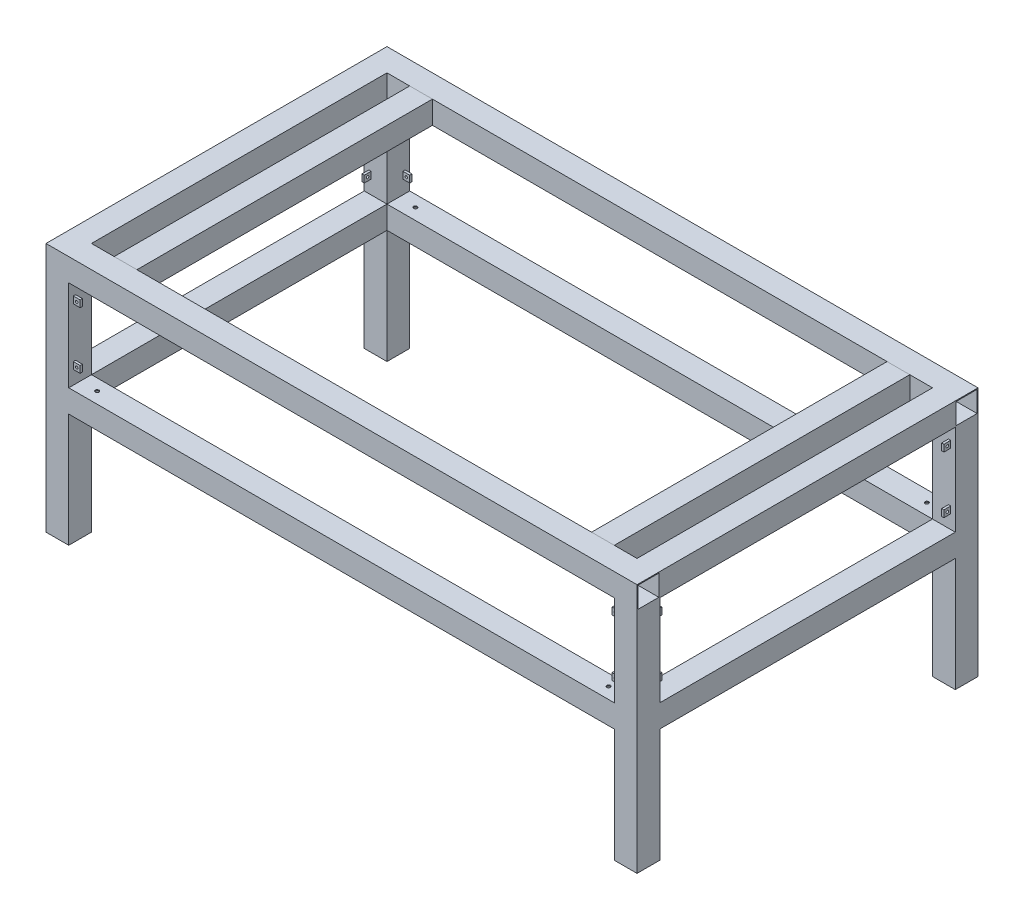
SolidWorks part; units mm, degrees
ref_plane "Plan de face" through (0, 0, 0) normal (0, 0, 1) x (1, 0, 0)
ref_plane "Plan de dessus" through (0, 0, 0) normal (0, 1, 0) x (1, 0, 0)
ref_plane "Plan de droite" through (0, 0, 0) normal (1, 0, 0) x (0, 0, -1)
sketch "Esquisse1" plane through (0, 0, 0) normal (0, 1, 0) x (1, 0, 0)
  line L1 (0, 0) -> (1300, 0)
  line L2 (0, 0) -> (0, 750)
  line L3 (0, 750) -> (1300, 750)
  line L4 (1300, 0) -> (1300, 750)
  line L5 (50, 700) -> (1250, 700)
  line L6 (50, 700) -> (50, 50)
  line L7 (50, 50) -> (1250, 50)
  line L8 (1250, 700) -> (1250, 50)
  dimension "D1" = 1300
  dimension "D2" = 750
  dimension "D3" = 50
  dimension "D4" = 50
  dimension "D5" = 50
  dimension "D6" = 50
extrude "Boss.-Extru.1" add sketch "Esquisse1" against normal blind 550
sketch "Esquisse2" plane through (0, 0, 0) normal (0, 0, 1) x (1, 0, 0)
  line L0 (0, 0) -> (1300, 0) construction
  line L1 (50, -50) -> (1250, -50)
  line L2 (50, -50) -> (50, -250)
  line L3 (50, -250) -> (1250, -250)
  line L4 (1250, -50) -> (1250, -250)
  line L5 (50, -300) -> (1250, -300)
  line L6 (50, -300) -> (50, -550)
  line L7 (50, -550) -> (1250, -550)
  line L8 (1250, -300) -> (1250, -550)
  line L9 (0, -550) -> (1300, -550) construction
  line L10 (1300, -550) -> (1300, 0) construction
  line L11 (0, -550) -> (0, 0) construction
  point P12 (1250, -425)
  dimension "D1" = 50
  dimension "D2" = 50
  dimension "D3" = 200
  dimension "D4" = 0
  dimension "D5" = 50
  dimension "D6" = 50
  dimension "D7" = 50
  dimension "D8" = 50
extrude "Enlèv. mat.-Extru.1" cut sketch "Esquisse2" against normal through all
sketch "Esquisse3" plane through (0, 0, 0) normal (-1, 0, 0) x (0, 0, 1)
  line L0 (-750, -550) -> (0, -550) construction
  line L1 (-700, -50) -> (-50, -50)
  line L2 (-700, -50) -> (-700, -250)
  line L3 (-700, -250) -> (-50, -250)
  line L4 (-50, -50) -> (-50, -250)
  line L5 (-700, -300) -> (-50, -300)
  line L6 (-700, -300) -> (-700, -550)
  line L7 (-700, -550) -> (-50, -550)
  line L8 (-50, -300) -> (-50, -550)
  line L9 (-750, 0) -> (0, 0) construction
  line L10 (0, -550) -> (0, 0) construction
  line L11 (-750, -550) -> (-750, 0) construction
  dimension "D1" = 50
  dimension "D2" = 50
  dimension "D3" = 50
  dimension "D4" = 50
  dimension "D5" = 50
  dimension "D6" = 200
  dimension "D7" = 50
extrude "Enlèv. mat.-Extru.2" cut sketch "Esquisse3" against normal through all
sketch "Esquisse4" plane through (0, 0, 0) normal (0, 1, 0) x (1, 0, 0)
  line L0 (1250, 700) -> (50, 700) construction
  line L1 (100, 700) -> (150, 700)
  line L2 (100, 700) -> (100, 50)
  line L3 (100, 50) -> (150, 50)
  line L4 (150, 700) -> (150, 50)
  line L5 (50, 50) -> (1250, 50) construction
  line L6 (50, 700) -> (50, 50) construction
  line L7 (1150, 700) -> (1200, 700)
  line L8 (1150, 700) -> (1150, 50)
  line L9 (1150, 50) -> (1200, 50)
  line L10 (1200, 700) -> (1200, 50)
  line L11 (1250, 50) -> (1250, 700) construction
  dimension "D1" = 50
  dimension "D2" = 50
  dimension "D3" = 50
  dimension "D4" = 50
extrude "Boss.-Extru.2" add sketch "Esquisse4" against normal blind 50 separate body
sketch "Esquisse5" plane through (1250, 0, 0) normal (-1, 0, 0) x (0, 0, 1)
  line L0 (-750, -250) -> (-750, -50) construction
  line L1 (-750, -80) -> (-735, -80)
  line L2 (-750, -80) -> (-750, -95)
  line L3 (-750, -95) -> (-735, -95)
  line L4 (-735, -80) -> (-735, -95)
  line L5 (-740, -80) -> (-740, -95)
  line L6 (-750, -205) -> (-735, -205)
  line L7 (-750, -205) -> (-750, -220)
  line L8 (-750, -220) -> (-735, -220)
  line L9 (-735, -205) -> (-735, -220)
  line L10 (-740, -205) -> (-740, -220)
  line L11 (-750, -50) -> (-700, -50) construction
  line L12 (-750, -250) -> (-700, -250) construction
  dimension "D1" = 10
  dimension "D2" = 5
  dimension "D3" = 5
  dimension "D4" = 15
  dimension "D5" = 15
  dimension "D6" = 30
  dimension "D7" = 30
extrude "Boss.-Extru.3" add sketch "Esquisse5" along normal blind 15 contours L1 L5 L3 L4 | L6 L10 L8 L9 region at (1250, -87.5, -737.5) region at (1250, -212.5, -737.5)
sketch "Esquisse6" plane through (0, 0, -700) normal (0, 0, 1) x (1, 0, 0)
  line L0 (1300, -50) -> (1300, -250) construction
  line L1 (1300, -80) -> (1285, -80)
  line L2 (1300, -80) -> (1300, -95)
  line L3 (1300, -95) -> (1285, -95)
  line L4 (1285, -80) -> (1285, -95)
  line L5 (1290, -80) -> (1290, -95)
  line L6 (1300, -220) -> (1285, -220)
  line L7 (1300, -220) -> (1300, -205)
  line L8 (1300, -205) -> (1285, -205)
  line L9 (1285, -220) -> (1285, -205)
  line L10 (1290, -205) -> (1290, -220)
  line L11 (1300, -50) -> (1250, -50) construction
  line L12 (1300, -250) -> (1250, -250) construction
  point P18 (1292.5, -220)
  dimension "D1" = 15
  dimension "D2" = 15
  dimension "D3" = 5
  dimension "D4" = 5
  dimension "D5" = 10
  dimension "D6" = 30
  dimension "D7" = 30
extrude "Boss.-Extru.4" add sketch "Esquisse6" along normal blind 15 contours L5 L1 L4 L3 | L10 L8 L9 L6 region at (1287.5, -87.5, -700) region at (1287.5, -212.5, -700)
sketch "Esquisse7" plane through (50, 0, 0) normal (1, 0, 0) x (0, 0, -1)
  line L0 (750, -50) -> (750, -250) construction
  line L1 (750, -80) -> (735, -80)
  line L2 (750, -80) -> (750, -95)
  line L3 (750, -95) -> (735, -95)
  line L4 (735, -80) -> (735, -95)
  line L5 (740, -80) -> (740, -95)
  line L6 (750, -220) -> (735, -220)
  line L7 (750, -220) -> (750, -205)
  line L8 (750, -205) -> (735, -205)
  line L9 (735, -220) -> (735, -205)
  line L10 (740, -205) -> (740, -220)
  line L11 (750, -250) -> (700, -250) construction
  line L12 (750, -50) -> (700, -50) construction
  dimension "D1" = 15
  dimension "D2" = 15
  dimension "D3" = 10
  dimension "D4" = 5
  dimension "D5" = 5
  dimension "D6" = 30
  dimension "D7" = 30
extrude "Boss.-Extru.5" add sketch "Esquisse7" along normal blind 15 contours L5 L1 L4 L3 | L10 L8 L9 L6 region at (50, -87.5, -737.5) region at (50, -212.5, -737.5)
sketch "Esquisse8" plane through (0, 0, -700) normal (0, 0, 1) x (1, 0, 0)
  line L0 (0, -50) -> (0, -250) construction
  line L1 (10, -80) -> (10, -95)
  line L2 (0, -80) -> (15, -80)
  line L3 (0, -80) -> (0, -95)
  line L4 (0, -95) -> (15, -95)
  line L5 (15, -80) -> (15, -95)
  line L6 (0, -205) -> (15, -205)
  line L7 (0, -205) -> (0, -220)
  line L8 (0, -220) -> (15, -220)
  line L9 (15, -205) -> (15, -220)
  line L10 (10, -205) -> (10, -220)
  line L11 (50, -250) -> (0, -250) construction
  line L13 (50, -50) -> (0, -50) construction
  point P16 (7.5, -220)
  dimension "D1" = 15
  dimension "D2" = 5
  dimension "D3" = 10
  dimension "D4" = 30
  dimension "D5" = 5
  dimension "D6" = 10
  dimension "D7" = 15
  dimension "D8" = 30
extrude "Boss.-Extru.6" add sketch "Esquisse8" along normal blind 15 contours L5 L2 L1 L4 | L6 L10 L8 L9 region at (12.5, -87.5, -700) region at (12.5, -212.5, -700)
sketch "Esquisse10" plane through (50, 0, 0) normal (1, 0, 0) x (0, 0, -1)
  line L0 (0, -50) -> (0, -250) construction
  line L1 (0, -80) -> (15, -80)
  line L2 (0, -80) -> (0, -95)
  line L3 (0, -95) -> (15, -95)
  line L4 (15, -80) -> (15, -95)
  line L5 (10, -80) -> (10, -95)
  line L6 (0, -205) -> (15, -205)
  line L7 (0, -205) -> (0, -220)
  line L8 (0, -220) -> (15, -220)
  line L9 (15, -205) -> (15, -220)
  line L10 (10, -205) -> (10, -220)
  line L11 (50, -250) -> (0, -250) construction
  line L12 (50, -50) -> (0, -50) construction
  point P18 (7.5, -80)
  dimension "D1" = 5
  dimension "D2" = 5
  dimension "D3" = 15
  dimension "D4" = 15
  dimension "D5" = 15
  dimension "D6" = 15
  dimension "D7" = 30
  dimension "D8" = 30
extrude "Boss.-Extru.7" add sketch "Esquisse10" along normal blind 15 contours L1 L5 L3 L4 | L6 L10 L8 L9 region at (50, -87.5, -12.5) region at (50, -212.5, -12.5)
sketch "Esquisse12" plane through (0, 0, -50) normal (0, 0, -1) x (-1, 0, 0)
  line L0 (0, -250) -> (0, -50) construction
  line L1 (0, -80) -> (-15, -80)
  line L2 (0, -80) -> (0, -95)
  line L3 (0, -95) -> (-15, -95)
  line L4 (-15, -80) -> (-15, -95)
  line L5 (-10, -80) -> (-10, -95)
  line L6 (0, -205) -> (-15, -205)
  line L7 (0, -205) -> (0, -220)
  line L8 (0, -220) -> (-15, -220)
  line L9 (-15, -205) -> (-15, -220)
  line L10 (-10, -205) -> (-10, -220)
  line L11 (-50, -50) -> (0, -50) construction
  line L12 (-50, -250) -> (0, -250) construction
  point P14 (-15, -87.5)
  dimension "D1" = 15
  dimension "D2" = 15
  dimension "D3" = 15
  dimension "D4" = 15
  dimension "D5" = 5
  dimension "D6" = 5
  dimension "D7" = 30
  dimension "D8" = 30
extrude "Boss.-Extru.8" add sketch "Esquisse12" along normal blind 15 contours L5 L1 L4 L3 | L10 L6 L9 L8 region at (12.5, -87.5, -50) region at (12.5, -212.5, -50)
sketch "Esquisse14" plane through (1250, 0, 0) normal (-1, 0, 0) x (0, 0, 1)
  line L0 (0, -250) -> (0, -50) construction
  line L1 (0, -80) -> (-15, -80)
  line L2 (0, -80) -> (0, -95)
  line L3 (0, -95) -> (-15, -95)
  line L4 (-15, -80) -> (-15, -95)
  line L5 (-10, -80) -> (-10, -95)
  line L6 (0, -205) -> (-15, -205)
  line L7 (0, -205) -> (0, -220)
  line L8 (0, -220) -> (-15, -220)
  line L9 (-15, -205) -> (-15, -220)
  line L10 (-10, -205) -> (-10, -220)
  line L11 (-50, -250) -> (0, -250) construction
  line L12 (-50, -50) -> (0, -50) construction
  point P18 (-15, -87.5)
  dimension "D1" = 15
  dimension "D2" = 5
  dimension "D3" = 15
  dimension "D4" = 30
  dimension "D5" = 30
  dimension "D6" = 5
  dimension "D7" = 15
  dimension "D8" = 15
extrude "Boss.-Extru.9" add sketch "Esquisse14" along normal blind 15 contours L5 L1 L4 L3 | L10 L6 L9 L8 region at (1250, -87.5, -12.5) region at (1250, -212.5, -12.5)
sketch "Esquisse15" plane through (0, 0, -50) normal (0, 0, -1) x (-1, 0, 0)
  line L0 (-1300, -250) -> (-1300, -50) construction
  line L1 (-1300, -80) -> (-1285, -80)
  line L2 (-1300, -80) -> (-1300, -95)
  line L3 (-1300, -95) -> (-1285, -95)
  line L4 (-1285, -80) -> (-1285, -95)
  line L5 (-1290, -80) -> (-1290, -95)
  line L6 (-1300, -205) -> (-1285, -205)
  line L7 (-1300, -205) -> (-1300, -220)
  line L8 (-1300, -220) -> (-1285, -220)
  line L9 (-1285, -205) -> (-1285, -220)
  line L10 (-1290, -205) -> (-1290, -220)
  line L11 (-1300, -50) -> (-1250, -50) construction
  line L12 (-1300, -250) -> (-1250, -250) construction
  point P14 (-1285, -212.5)
  point P15 (-1300, -212.5)
  dimension "D1" = 15
  dimension "D2" = 15
  dimension "D3" = 15
  dimension "D4" = 5
  dimension "D5" = 15
  dimension "D6" = 30
  dimension "D7" = 30
extrude "Boss.-Extru.10" add sketch "Esquisse15" along normal blind 15 contours L6 L10 L8 L9 | L1 L5 L3 L4 region at (1287.5, -87.5, -50) region at (1287.5, -212.5, -50)
sketch "Esquisse16" plane through (1290, 0, 0) normal (1, 0, 0) x (0, 0, -1)
  line L0 (65, -95) -> (50, -95) construction
  line L1 (65, -80) -> (50, -80) construction
  line L2 (65, -80) -> (65, -95) construction
  line L3 (50, -80) -> (50, -95) construction
  line L4 (65, -205) -> (65, -220) construction
  line L5 (65, -220) -> (50, -220) construction
  line L6 (685, -80) -> (685, -95) construction
  line L7 (685, -80) -> (700, -80) construction
  line L8 (685, -205) -> (685, -220) construction
  line L9 (685, -205) -> (700, -205) construction
  circle A0 centre (57.5, -87.5) radius 2.75
  circle A1 centre (57.5, -212.5) radius 2.75
  circle A2 centre (692.5, -87.5) radius 2.75
  circle A3 centre (692.5, -212.5) radius 2.75
  dimension "D5" = 5.5
  dimension "D6" = 5.5
  dimension "D9" = 5.5
  dimension "D12" = 5.5
  dimension "D1" = 15
  dimension "D2" = 7.5
  dimension "D3" = 15
  dimension "D4" = 7.5
  dimension "D7" = 7.5
  dimension "D8" = 7.5
  dimension "D10" = 7.5
  dimension "D11" = 7.5
  dimension "D13" = 7.5
  dimension "D14" = 7.5
extrude "Enlèv. mat.-Extru.3" cut sketch "Esquisse16" against normal blind 1500
sketch "Esquisse17" plane through (0, 0, -10) normal (0, 0, 1) x (1, 0, 0)
  line L0 (65, -205) -> (50, -205) construction
  line L1 (65, -205) -> (65, -220) construction
  line L2 (65, -80) -> (50, -80) construction
  line L3 (65, -80) -> (65, -95) construction
  line L4 (1235, -80) -> (1235, -95) construction
  line L5 (1235, -95) -> (1250, -95) construction
  line L6 (1235, -205) -> (1250, -205) construction
  line L8 (1235, -205) -> (1235, -220) construction
  circle A0 centre (57.5, -87.5) radius 2.75
  circle A1 centre (57.5, -212.5) radius 2.75
  circle A2 centre (1242.5, -212.5) radius 2.75
  circle A3 centre (1242.5, -87.5) radius 2.75
  dimension "D1" = 5.5
  dimension "D2" = 5.5
  dimension "D3" = 5.5
  dimension "D4" = 5.5
  dimension "D5" = 7.5
  dimension "D6" = 7.5
  dimension "D7" = 7.5
  dimension "D8" = 7.5
  dimension "D9" = 7.5
  dimension "D10" = 7.5
  dimension "D11" = 7.5
  dimension "D12" = 7.5
extrude "Enlèv. mat.-Extru.4" cut sketch "Esquisse17" against normal blind 1000
sketch "Esquisse18" plane through (0, -250, 0) normal (0, 1, 0) x (1, 0, 0)
  line L0 (50, 0) -> (1250, 0) construction
  line L1 (50, 750) -> (1250, 750) construction
  line L2 (1250, 750) -> (1250, 700) construction
  line L3 (50, 750) -> (50, 700) construction
  line L4 (1250, 50) -> (1250, 0) construction
  line L5 (50, 50) -> (50, 0) construction
  circle A0 centre (1212.5, 25) radius 4
  circle A1 centre (87.5, 25) radius 4
  circle A2 centre (87.5, 725) radius 4
  circle A3 centre (1212.5, 725) radius 4
  dimension "D1" = 8
  dimension "D2" = 8
  dimension "D3" = 8
  dimension "D4" = 8
  dimension "D5" = 1125
  dimension "D6" = 1125
  dimension "D7" = 25
  dimension "D8" = 25
  dimension "D9" = 25
  dimension "D10" = 25
  dimension "D11" = 700
  dimension "D12" = 700
  dimension "D13" = 37.5
  dimension "D14" = 37.5
  dimension "D15" = 37.5
  dimension "D16" = 37.5
extrude "Enlèv. mat.-Extru.5" cut sketch "Esquisse18" against normal blind 80
sketch "Esquisse19" plane through (0, -300, 0) normal (0, -1, 0) x (-1, 0, 0)
  circle A0 centre (-1212.5, 725) radius 15
  circle A1 centre (-87.5, 725) radius 15
  circle A2 centre (-87.5, 25) radius 15
  circle A3 centre (-1212.5, 25) radius 15
  dimension "D1" = 30
  dimension "D2" = 30
  dimension "D3" = 30
  dimension "D4" = 30
extrude "Enlèv. mat.-Extru.6" cut sketch "Esquisse19" against normal blind 48
sketch "Esquisse20" plane through (0, 0, 0) normal (-1, 0, 0) x (0, 0, 1)
  line L0 (-750, 0) -> (0, 0) construction
  line L1 (-2, -2) -> (-48, -2)
  line L2 (-2, -2) -> (-2, -48)
  line L3 (-2, -48) -> (-48, -48)
  line L4 (-48, -2) -> (-48, -48)
  line L5 (-702, -2) -> (-748, -2)
  line L6 (-702, -2) -> (-702, -48)
  line L7 (-702, -48) -> (-748, -48)
  line L8 (-748, -2) -> (-748, -48)
  line L9 (-750, -550) -> (-750, 0) construction
  line L10 (0, -550) -> (0, 0) construction
  dimension "D1" = 2
  dimension "D2" = 2
  dimension "D3" = 46
  dimension "D4" = 46
  dimension "D5" = 2
  dimension "D6" = 46
  dimension "D7" = 46
  dimension "D8" = 2
extrude "Enlèv. mat.-Extru.7" cut sketch "Esquisse20" against normal blind 10000
sketch "Esquisse21" plane through (0, -550, 0) normal (0, -1, 0) x (-1, 0, 0)
  line L0 (0, 0) -> (-50, 0) construction
  line L1 (-1252, 2) -> (-1298, 2)
  line L2 (-1252, 2) -> (-1252, 48)
  line L3 (-1252, 48) -> (-1298, 48)
  line L4 (-1298, 2) -> (-1298, 48)
  line L5 (-1252, 702) -> (-1298, 702)
  line L6 (-1252, 702) -> (-1252, 748)
  line L7 (-1252, 748) -> (-1298, 748)
  line L8 (-1298, 702) -> (-1298, 748)
  line L9 (-2, 702) -> (-48, 702)
  line L10 (-2, 702) -> (-2, 748)
  line L11 (-2, 748) -> (-48, 748)
  line L12 (-48, 702) -> (-48, 748)
  line L13 (-2, 2) -> (-48, 2)
  line L14 (-2, 2) -> (-2, 48)
  line L15 (-2, 48) -> (-48, 48)
  line L16 (-48, 2) -> (-48, 48)
  line L17 (-50, 50) -> (-50, 0) construction
  line L18 (-50, 50) -> (0, 50) construction
  line L19 (-50, 700) -> (0, 700) construction
  line L20 (-50, 750) -> (-50, 700) construction
  line L21 (-1300, 700) -> (-1250, 700) construction
  line L22 (-1300, 700) -> (-1300, 750) construction
  line L23 (-1250, 0) -> (-1300, 0) construction
  line L24 (-1300, 0) -> (-1300, 50) construction
  dimension "D1" = 46
  dimension "D2" = 2
  dimension "D3" = 2
  dimension "D4" = 2
  dimension "D5" = 46
  dimension "D6" = 46
  dimension "D7" = 2
  dimension "D8" = 2
  dimension "D9" = 46
  dimension "D10" = 46
  dimension "D11" = 2
  dimension "D12" = 2
  dimension "D13" = 46
  dimension "D14" = 46
  dimension "D15" = 2
  dimension "D16" = 2
extrude "Enlèv. mat.-Extru.8" cut sketch "Esquisse21" against normal blind 500
